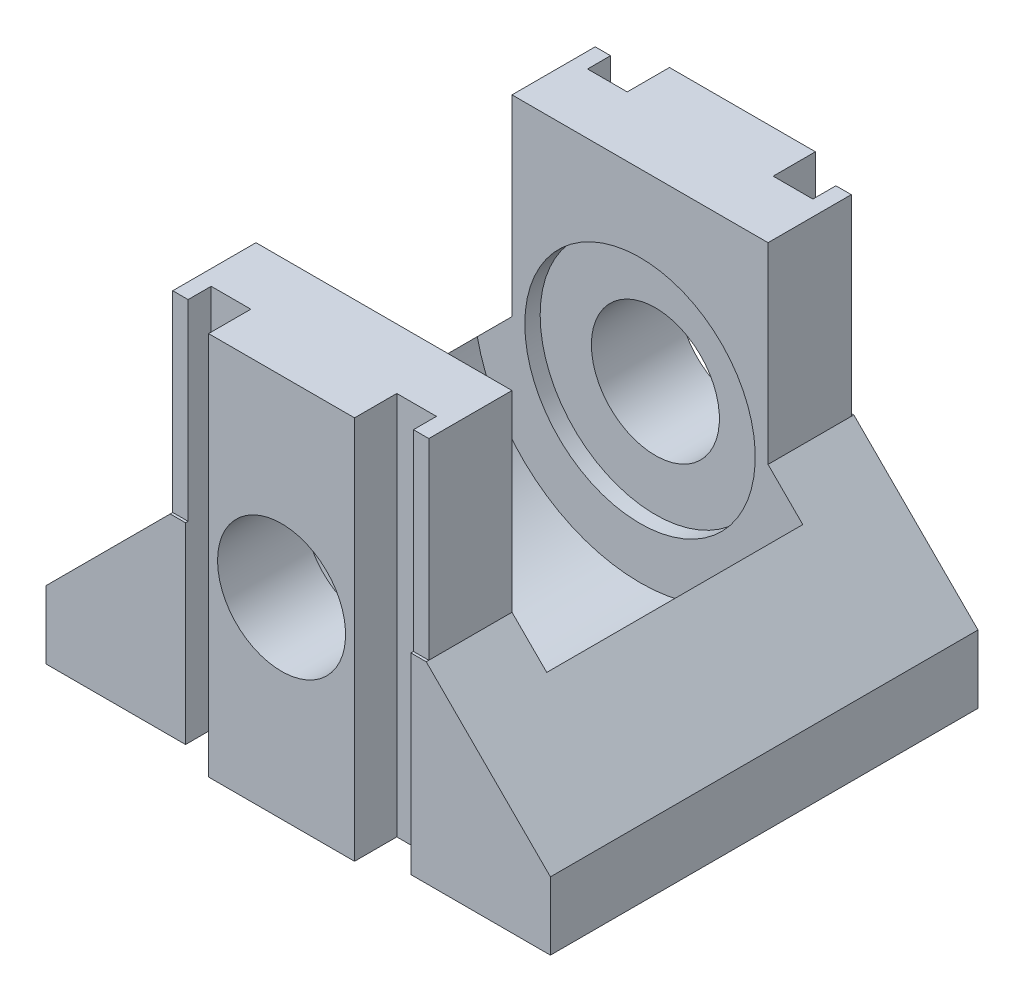
SolidWorks part; units mm, degrees
ref_plane "Płaszczyzna przednia" through (0, 0, 0) normal (0, 0, 1) x (1, 0, 0)
ref_plane "Płaszczyzna górna" through (0, 0, 0) normal (0, 1, 0) x (1, 0, 0)
ref_plane "Płaszczyzna prawa" through (0, 0, 0) normal (1, 0, 0) x (0, 0, -1)
sketch "Sketch5" plane through (0, 0, 0) normal (0, 0, 1) x (1, 0, 0)
  line L1 (-40, 15) -> (0, 15)
  line L2 (-40, 15) -> (-40, 0)
  line L3 (-40, 0) -> (0, 0)
  line L4 (0, 15) -> (0, 0)
  dimension "D1" = 40
  dimension "D2" = 15
extrude "Boss-Extrude2" add sketch "Sketch5" along normal blind 17
sketch "Sketch6" plane through (0, 0, 0) normal (0, 0, -1) x (-1, 0, 0)
  line L0 (0, 15) -> (40, 15) construction
  circle A0 centre (20, 15) radius 13
  dimension "D1" = 26
extrude "Cut-Extrude4" cut sketch "Sketch6" against normal blind 10
sketch "Sketch7" plane through (0, 0, 17) normal (0, 0, 1) x (1, 0, 0)
  line L0 (0, 15) -> (-40, 15) construction
  circle A0 centre (-20, 15) radius 2.5
  dimension "D1" = 5
extrude "Cut-Extrude5" cut sketch "Sketch7" against normal blind 4.5 contours A0
mirror "Mirror5" about plane through (0, 0, 0) normal (0, 0, 1) of "Cut-Extrude4", "Cut-Extrude5", "Boss-Extrude2"
sketch "Sketch8" plane through (0, 0, 0) normal (0, -1, 0) x (1, 0, 0)
  line L0 (-40, 0) -> (0, 0) construction
  line L1 (-20, 17) -> (-20, -17) construction
  line L2 (-40, 17) -> (-40, -17) construction
  line L3 (0, 17) -> (0, -17) construction
  line L4 (-40, -17) -> (0, -17) construction
  line L5 (-40, 17) -> (0, 17) construction
  circle A0 centre (-33, 11.5) radius 4.8
  circle A1 centre (-7, 11.5) radius 4.8
  circle A2 centre (-7, -11.5) radius 4.8
  circle A3 centre (-33, -11.5) radius 4.8
  dimension "D1" = 9.6
  dimension "D2" = 5.5
  dimension "D3" = 7
chamfer "Chamfer8" distance 10 angle 45 2 edges at (-40, 15, 0) (0, 15, 0)
sketch "Sketch10" plane through (0, 0, -10) normal (0, 0, 1) x (1, 0, 0)
  line L0 (-30, 15) -> (-22.5, 15)
  line L1 (-17.5, 15) -> (-10, 15)
  line L2 (-30, 30) -> (-10, 30)
  line L3 (-30, 30) -> (-30, 15)
  line L4 (-30, 15) -> (-22.5, 15)
  line L5 (-10, 30) -> (-10, 15)
  line L6 (-17.5, 15) -> (-10, 15)
  circle A0 centre (-20, 15) radius 2.5
  arc A1 (-30, 15) -> (-10, 15) centre (-20, 15) ccw
  arc A2 (-22.5, 15) -> (-17.5, 15) centre (-20, 15) ccw construction
  circle A3 centre (-20, 15) radius 10 construction
  line M3 (-10, 15) -> (-30, 15)
  line M7 (-10, 15) -> (-30, 15)
  dimension "D1" = 15
extrude "Boss-Extrude3" add sketch "Sketch10" against normal blind 6.5 contours A0 L5 L2 L3 M7 M3 | A0 region at (-20, 22.7178, -10)
ref_plane "Plane1" through (0, 0, 0) normal (0, 0, -1) x (-1, 0, 0)
mirror "Mirror6" about plane through (0, 0, 0) normal (0, 0, -1) of "Boss-Extrude3"
extrude "Cut-Extrude8" cut sketch "Sketch8" against normal blind 3
sketch "Sketch9" plane through (0, 0, 0) normal (0, -1, 0) x (1, 0, 0)
  line L0 (-20, 17) -> (-20, -17) construction
  line L1 (-40, 0) -> (0, 0) construction
  line L3 (-40, 17) -> (0, 17) construction
  line L4 (-40, 17) -> (-40, -17) construction
  line L5 (-40, -17) -> (0, -17) construction
  line L6 (0, 17) -> (0, -17) construction
  line L7 (-11.5, 15) -> (-14, 15)
  line L8 (-28.5, 17) -> (-26, 17)
  line L9 (-28.5, 17) -> (-28.5, 15)
  line L10 (-28.5, 15) -> (-26, 15)
  line L11 (-26, 17) -> (-26, 15)
  line L12 (-14, 17) -> (-14, 15)
  line L13 (-11.5, 17) -> (-14, 17)
  line L14 (-11.5, 17) -> (-11.5, 15)
  line L15 (-11.5, -17) -> (-11.5, -15)
  line L16 (-11.5, -17) -> (-14, -17)
  line L17 (-14, -17) -> (-14, -15)
  line L18 (-11.5, -15) -> (-14, -15)
  line L19 (-28.5, -15) -> (-26, -15)
  line L20 (-26, -17) -> (-26, -15)
  line L21 (-28.5, -17) -> (-26, -17)
  line L22 (-28.5, -17) -> (-28.5, -15)
  dimension "D1" = 2.5
  dimension "D2" = 2
  dimension "D3" = 6
extrude "Cut-Extrude7" cut sketch "Sketch9" against normal blind 52
sketch "Sketch11" plane through (0, 0, 10) normal (0, 0, -1) x (-1, 0, 0)
  circle A0 centre (20, 15) radius 5
  arc A1 (7.2864, 12.2864) -> (32.7136, 12.2864) centre (20, 15) ccw construction
  dimension "D1" = 10
extrude "Cut-Extrude9" cut sketch "Sketch11" against normal mid plane 90
sketch "Sketch12" plane through (0, 0, 10) normal (0, 0, -1) x (-1, 0, 0)
  circle A0 centre (20, 15) radius 5
  circle A1 centre (20, 15) radius 5 construction
  circle A2 centre (20, 15) radius 9
  dimension "D1" = 18
extrude "Cut-Extrude11" cut sketch "Sketch12" against normal blind 1.2
mirror "Mirror7" about plane through (0, 0, 0) normal (0, 0, -1) of "Cut-Extrude11"
sketch "Sketch13" plane through (0, 0, 0) normal (0, -1, 0) x (1, 0, 0)
  line L20 (-25.7, 14.7) -> (-28.8, 14.7)
  line L26 (-28.8, 14.7) -> (-28.8, 16.7)
  line L27 (-28.8, 16.7) -> (-39.7, 16.7)
  line L30 (-39.7, 16.7) -> (-39.7, -16.7)
  line L31 (-39.7, -16.7) -> (-28.8, -16.7)
  line L36 (-28.8, -16.7) -> (-28.8, -14.7)
  line L37 (-28.8, -14.7) -> (-25.7, -14.7)
  line L60 (-25.7, -14.7) -> (-25.7, -16.7)
  line L61 (-25.7, -16.7) -> (-14.3, -16.7)
  line L62 (-14.3, -16.7) -> (-14.3, -14.7)
  line L63 (-14.3, -14.7) -> (-11.2, -14.7)
  line L64 (-11.2, -14.7) -> (-11.2, -16.7)
  line L65 (-11.2, -16.7) -> (-0.3, -16.7)
  line L66 (-0.3, -16.7) -> (-0.3, 16.7)
  line L67 (-0.3, 16.7) -> (-11.2, 16.7)
  line L68 (-11.2, 16.7) -> (-11.2, 14.7)
  line L69 (-11.2, 14.7) -> (-14.3, 14.7)
  line L70 (-14.3, 14.7) -> (-14.3, 16.7)
  line L71 (-14.3, 16.7) -> (-25.7, 16.7)
  line L72 (-25.7, 16.7) -> (-25.7, 14.7)
  line L73 (-26, 15) -> (-28.5, 15)
  line L74 (-28.5, 15) -> (-28.5, 17)
  line L75 (-28.5, 17) -> (-40, 17)
  line L76 (-40, 17) -> (-40, -17)
  line L77 (-40, -17) -> (-28.5, -17)
  line L78 (-28.5, -17) -> (-28.5, -15)
  line L79 (-28.5, -15) -> (-26, -15)
  line L80 (-26, -15) -> (-26, -17)
  line L81 (-26, -17) -> (-14, -17)
  line L84 (-14, -17) -> (-14, -15)
  line L85 (-14, -15) -> (-11.5, -15)
  line L86 (-11.5, -15) -> (-11.5, -17)
  line L87 (-11.5, -17) -> (0, -17)
  line L88 (0, -17) -> (0, 17)
  line L89 (0, 17) -> (-11.5, 17)
  line L90 (-11.5, 17) -> (-11.5, 15)
  line L91 (-11.5, 15) -> (-14, 15)
  line L92 (-14, 15) -> (-14, 17)
  line L93 (-14, 17) -> (-26, 17)
  line L94 (-26, 17) -> (-26, 15)
  line L95 (-26, 15) -> (-28.5, 15)
  line L96 (-28.5, 15) -> (-28.5, 17)
  line L97 (-28.5, 17) -> (-40, 17)
  line L98 (-40, 17) -> (-40, -17)
  line L99 (-40, -17) -> (-28.5, -17)
  line L100 (-28.5, -17) -> (-28.5, -15)
  line L101 (-28.5, -15) -> (-26, -15)
  line L102 (-26, -15) -> (-26, -17)
  line L103 (-26, -17) -> (-14, -17)
  line L104 (-14, -17) -> (-14, -15)
  line L105 (-14, -15) -> (-11.5, -15)
  line L106 (-11.5, -15) -> (-11.5, -17)
  line L107 (-11.5, -17) -> (0, -17)
  line L108 (0, -17) -> (0, 17)
  line L109 (0, 17) -> (-11.5, 17)
  line L110 (-11.5, 17) -> (-11.5, 15)
  line L111 (-11.5, 15) -> (-14, 15)
  line L112 (-14, 15) -> (-14, 17)
  line L113 (-14, 17) -> (-26, 17)
  line L114 (-26, 17) -> (-26, 15)
  dimension "D1" = 0
  dimension "D2" = 0.3
extrude "Cut-Extrude12" cut sketch "Sketch13" against normal through all
sketch "Sketch14" plane through (0, 0, -16.7) normal (0, 0, -1) x (-1, 0, 0)
  line L15 (15, 15) -> (14.3, 15)
  line L16 (14.3, 15) -> (14.3, 0)
  line L17 (14.3, 0) -> (25.7, 0)
  line L18 (25.7, 0) -> (25.7, 15)
  line L19 (25.7, 15) -> (25, 15)
  line L20 (15, 15) -> (14.3, 15)
  line L21 (14.3, 15) -> (14.3, 0)
  line L22 (14.3, 0) -> (25.7, 0)
  line L23 (25.7, 0) -> (25.7, 15)
  line L24 (25.7, 15) -> (25, 15)
  arc A3 (15, 15) -> (25, 15) centre (20, 15) ccw
  arc A4 (15, 15) -> (25, 15) centre (20, 15) ccw
  dimension "D1" = 0
extrude "Boss-Extrude4" add sketch "Sketch14" along normal blind 1.3
extrude "Boss-Extrude8" add sketch "Sketch14<3>" against normal blind 1.3 from surface starting at face at (-20, 9.1667, 16.7)
sketch "Sketch14<3>" plane through (0, 0, -16.7) normal (0, 0, -1) x (-1, 0, 0) same geometry as "Sketch14"
sketch "Sketch16" plane through (0, 0, 16.5) normal (0, 0, 1) x (1, 0, 0)
  line L5 (-25.7, 30) -> (-25.7, 15)
  line L6 (-25.7, 15) -> (-25, 15)
  line L7 (-15, 15) -> (-14.3, 15)
  line L8 (-14.3, 15) -> (-14.3, 30)
  line L9 (-14.3, 30) -> (-25.7, 30)
  line L10 (-25.7, 30) -> (-25.7, 15)
  line L11 (-25.7, 15) -> (-25, 15)
  line L12 (-15, 15) -> (-14.3, 15)
  line L13 (-14.3, 15) -> (-14.3, 30)
  line L14 (-14.3, 30) -> (-25.7, 30)
  arc A1 (-15, 15) -> (-25, 15) centre (-20, 15) ccw
  arc A2 (-15, 15) -> (-25, 15) centre (-20, 15) ccw
  dimension "D1" = 0
extrude "Boss-Extrude9" add sketch "Sketch16" along normal up to surface (1.5 mm away) up to face at (-20, 9.1667, 18)
extrude "Boss-Extrude10" add sketch "Sketch16<2>" against normal up to surface (34.5 mm away) from surface up to face at (-20, 9.1667, -18) starting at face at (-20, 20.8333, -16.5)
sketch "Sketch16<2>" plane through (0, 0, 16.5) normal (0, 0, 1) x (1, 0, 0) same geometry as "Sketch16"
